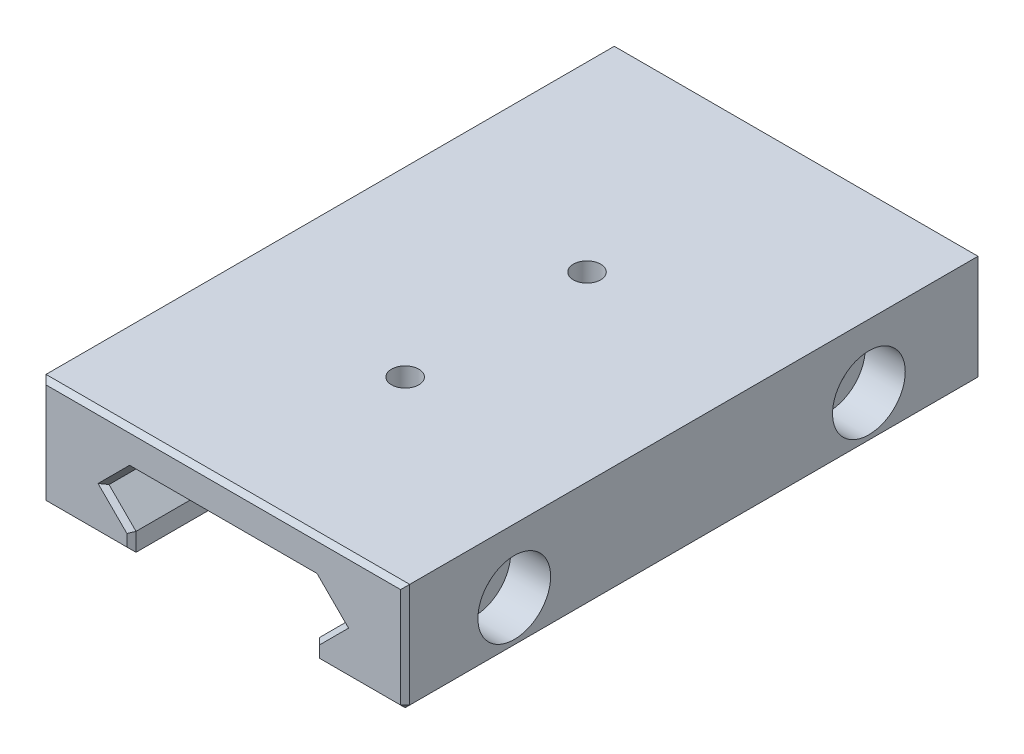
SolidWorks part; units mm, degrees
ref_plane "Ebene vorne" through (0, 0, 0) normal (0, 0, 1) x (1, 0, 0)
ref_plane "Ebene oben" through (0, 0, 0) normal (0, 1, 0) x (1, 0, 0)
ref_plane "Ebene rechts" through (0, 0, 0) normal (1, 0, 0) x (0, 0, -1)
sketch "Skizze1" plane through (0, 0, 0) normal (0, 0, 1) x (1, 0, 0)
  line L1 (-63.0762, -14.2199) -> (-23.0762, -14.2199)
  line L2 (-63.0762, -14.2199) -> (-63.0762, -26.2199)
  line L3 (-63.0762, -26.2199) -> (-23.0762, -26.2199)
  line L4 (-23.0762, -14.2199) -> (-23.0762, -26.2199)
  dimension "D1" = 12
  dimension "D2" = 40
extrude "Aufsatz-Linear austragen1" add sketch "Skizze1" along normal blind 63
sketch "Skizze2" plane through (0, 0, 0) normal (0, 0, -1) x (-1, 0, 0)
  line L0 (32.9762, -26.2199) -> (32.9762, -24.2199)
  line L1 (63.0762, -26.2199) -> (23.0762, -26.2199) construction
  line L2 (32.9762, -24.2199) -> (30.0063, -21.25)
  line L3 (30.0063, -21.25) -> (32.9762, -18.2802)
  line L4 (32.9762, -18.2802) -> (53.1762, -18.2802)
  line L5 (53.1762, -18.2802) -> (56.146, -21.25)
  line L6 (56.146, -21.25) -> (53.1762, -24.2199)
  line L7 (53.1762, -24.2199) -> (53.1762, -26.2199)
  line L9 (23.0762, -26.2199) -> (23.0762, -14.2199) construction
  dimension "D1" = 4.2
  dimension "D2" = 20.2
  dimension "D3" = 135
  dimension "D4" = 9.9
  dimension "D5" = 2
extrude "Schnitt-Linear austragen2" cut sketch "Skizze2" against normal through all and the other way through all flip side to cut
ref_plane "Ebene1" through (-43.0762, 0, 0) normal (1, 0, 0) x (0, 0, -1)
ref_axis "Achse1" through (-43.0762, -14.2199, 63) along (0, 1, 0)
hole_wizard "Stirnsenkung für M3" positions "Skizze12" profile "Skizze11" counterbore size "M4" standard "ISO" end condition through all
sketch "Skizze12" plane through (-23.0762, 0, 0) normal (1, 0, 0) x (0, 0, -1)
  line L0 (-63, -26.2199) -> (-63, -14.2199) construction
  line L1 (-63, -26.2199) -> (0, -26.2199) construction
  point P2 (-51, -21.2199)
  dimension "D1" = 12
  dimension "D2" = 5
sketch "Skizze11" plane through (-23.0762, -21.2199, 51) normal (0, 1, 0) x (0, 0, -1)
  line L0 (0, 0) -> (0, 40)
  line L1 (0, 40) -> (2.25, 40)
  line L3 (2.25, 40) -> (2.25, 4.4)
  line L4 (2.25, 4.4) -> (4, 4.4)
  line L5 (4, 4.4) -> (4, 0)
  line L7 (4, 0) -> (0, 0)
  line L11 (0, -6.35) -> (0, 107.95) construction
  dimension "Bohrerdurchmesser" = 4.5
  dimension "Bohrungstiefe" = 40
  dimension "Senkdurchmesser2" = 8
  dimension "Senktiefe2" = 4.4
sketch "Skizze13" plane through (-63.0762, 0, 0) normal (-1, 0, 0) x (0, 0, 1)
  line L1 (46.9585, -21.2199) -> (48.9793, -24.7199)
  line L2 (48.9793, -24.7199) -> (53.0207, -24.7199)
  line L3 (53.0207, -24.7199) -> (55.0415, -21.2199)
  line L4 (55.0415, -21.2199) -> (53.0207, -17.7199)
  line L5 (53.0207, -17.7199) -> (48.9793, -17.7199)
  line L6 (48.9793, -17.7199) -> (46.9585, -21.2199)
  circle A0 centre (51, -21.2199) radius 3.5 construction
  dimension "D1" = 7
extrude "Schnitt-Linear austragen3" cut sketch "Skizze13" against normal blind 3.2
pattern_linear "Lineares Muster2" count 2 spacing 39 along (0, 0, -1) of "Schnitt-Linear austragen3", "Stirnsenkung für M3"
sketch "Skizze15" plane through (0, -14.2199, 0) normal (0, 1, 0) x (1, 0, 0)
  line L0 (-25.5762, 0) -> (-25.5762, -4)
  line L2 (-25.5762, -4) -> (-43.0762, -4)
  line L3 (-43.0762, -4) -> (-43.0762, 0)
  line L4 (-63.0762, 0) -> (-23.0762, 0) construction
  line L5 (-43.0762, 0) -> (-25.5762, 0)
  dimension "D1" = 4
  dimension "D2" = 2.5
chamfer "Fase1" distance 0.5 angle 45 23 edges at (-58.1262, -26.2199, 63) (-63.0762, -26.2199, 31.5) (-63.0762, -20.2199, 63) (-43.0762, -14.2199, 63) (-28.0262, -26.2199, 63) (-23.0762, -26.2199, 31.5) (-23.0762, -20.2199, 63) (-43.0762, -18.2802, 63) (-43.0762, -18.2802, 0) (-32.9762, -25.2199, 63) (-53.1762, -25.2199, 63) (-32.9762, -25.2199, 0) (-53.1762, -25.2199, 0) (-58.1262, -26.2199, 0) (-28.0262, -26.2199, 0) (-31.4913, -19.7651, 63) (-31.4913, -22.7349, 63) (-54.6611, -19.7651, 63) (-54.6611, -22.7349, 63) (-54.6611, -19.7651, 0) (-54.6611, -22.7349, 0) (-31.4913, -19.7651, 0) (-31.4913, -22.7349, 0)
sketch "Sketch1" plane through (0, -14.2199, 0) normal (0, 1, 0) x (1, 0, 0)
  line L0 (-43.0762, -21.7553) -> (-43.0762, 21.7553) construction
  line L1 (-37.0762, -48) -> (-49.0762, -48)
  line L2 (-37.0762, -48) -> (-37.0762, -8)
  line L3 (-37.0762, -8) -> (-49.0762, -8)
  line L4 (-49.0762, -48) -> (-49.0762, -8)
  line L5 (-37.0762, -48) -> (-49.0762, -8) construction
  line L6 (-37.0762, -8) -> (-49.0762, -48) construction
  point P0 (-43.0762, -28)
  dimension "D1" = 0
  dimension "D2" = 12
  dimension "D3" = 40
  dimension "D4" = 15
extrude "Boss-Extrude1" add sketch "Sketch1" along normal blind 10
sketch "Sketch2" plane through (0, 0, 48) normal (0, 0, 1) x (1, 0, 0)
  line L0 (-49.0762, -4.2199) -> (-37.0762, -4.2199) construction
  circle A0 centre (-43.0762, -4.2199) radius 6
extrude "Boss-Extrude2" add sketch "Sketch2" against normal blind 40
sketch "Sketch5" plane through (0, 0, 48) normal (0, 0, 1) x (1, 0, 0)
  line L0 (-37.0762, -4.2199) -> (-37.0762, -14.2199) construction
  circle A0 centre (-43.0762, -4.2199) radius 3
  dimension "D3" = 6
  dimension "D1" = 0
  dimension "D2" = 6
extrude "Cut-Extrude1" cut sketch "Sketch5" against normal blind 40 from offset 10 offset against normal yes
sketch "Sketch6" plane through (0, 0, 48) normal (0, 0, 1) x (1, 0, 0)
  line L0 (-37.0762, -4.2199) -> (-37.0762, -14.2199) construction
  circle A0 centre (-43.0762, -4.2199) radius 1.25
  dimension "D2" = 2.5
  dimension "D1" = 6
extrude "Cut-Extrude2" cut sketch "Sketch6" against normal through all
sketch "Sketch8" plane through (-43.0762, 0, 0) normal (1, 0, 0) x (0, 0, -1)
  line L0 (-51.094, -8.6906) -> (-9.7971, 6.3403)
  line L1 (-9.7971, 6.3403) -> (-51.094, 6.3403)
  line L2 (-51.094, 6.3403) -> (-51.094, -8.6906)
  dimension "D1" = 70
extrude "Cut-Extrude3" cut sketch "Sketch8" against normal through all and the other way through all
fillet "Fillet1" radius 3 4 edges at (-49.0762, -5.8922, 43.4054) (-43.0762, -7.5645, 48) (-37.0762, -5.8922, 43.4054) (-43.0762, 1.7801, 22.326)
sketch "Sketch9" plane through (0, -14.2199, 0) normal (0, 1, 0) x (1, 0, 0)
  line L0 (-49.0762, -48) -> (-37.0762, -48) construction
  line L1 (-37.0762, -48) -> (-37.0762, -8) construction
  circle A0 centre (-43.0762, -43) radius 1.5
  circle A1 centre (-43.0762, -23) radius 1.5
  dimension "D1" = 3
  dimension "D2" = 5
  dimension "D3" = 6
  dimension "D4" = 2
extrude "Cut-Extrude4" cut sketch "Sketch9" against normal through all and the other way through all
sketch "Sketch10" plane through (-63.0762, 0, 0) normal (-1, 0, 0) x (0, 0, 1)
  line L1 (0, -14.2199) -> (63.3574, -14.2199)
  line L2 (0, -14.2199) -> (0, 14.5862)
  line L3 (0, 14.5862) -> (63.3574, 14.5862)
  line L4 (63.3574, -14.2199) -> (63.3574, 14.5862)
extrude "Cut-Extrude5" cut sketch "Sketch10" against normal through all
